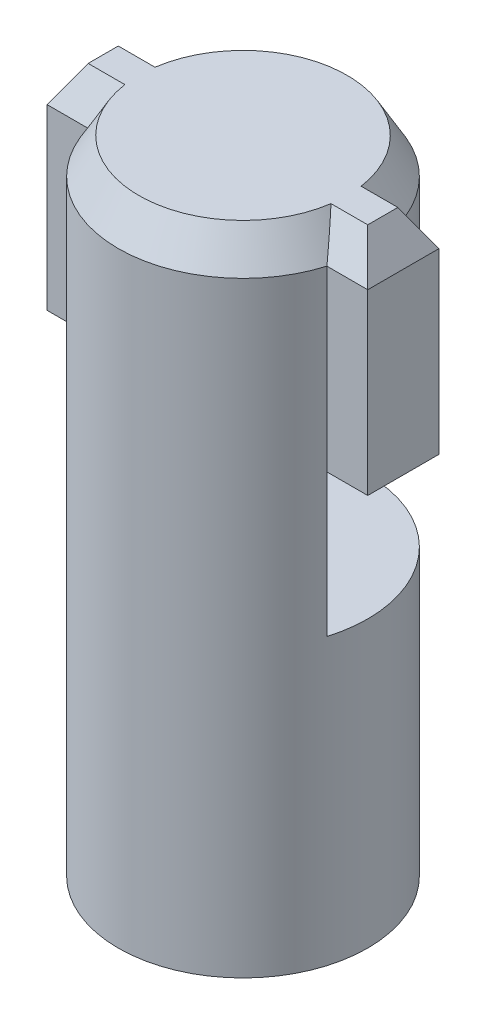
SolidWorks part; units mm, degrees
ref_plane "Спереди" through (0, 0, 0) normal (0, 0, 1) x (1, 0, 0)
ref_plane "Сверху" through (0, 0, 0) normal (0, 1, 0) x (1, 0, 0)
ref_plane "Справа" through (0, 0, 0) normal (1, 0, 0) x (0, 0, -1)
sketch "Sketch1" plane through (0, 0, 0) normal (0, 1, 0) x (1, 0, 0)
  circle A0 centre (0, 0) radius 3.5
  dimension "D1" = 7
extrude "Boss-Extrude1" add sketch "Sketch1" along normal blind 18
sketch "Sketch2" plane through (0, 18, 0) normal (0, 1, 0) x (1, 0, 0)
  line L1 (4.5, 1) -> (-4.5, 1)
  line L2 (4.5, 1) -> (4.5, -1)
  line L3 (4.5, -1) -> (-4.5, -1)
  line L4 (-4.5, 1) -> (-4.5, -1)
  line L5 (4.5, 1) -> (-4.5, -1) construction
  line L6 (4.5, -1) -> (-4.5, 1) construction
  point P0 (0, 0)
  dimension "D1" = 2
  dimension "D2" = 9
extrude "Boss-Extrude3" add sketch "Sketch2" against normal blind 10
sketch "Sketch3" plane through (0, 0, 0) normal (0, -1, 0) x (1, 0, 0)
  line L0 (3.3541, 1) -> (-3.3541, 1) construction
  line L1 (-3.5, 0) -> (3.5, 0) construction
  line L3 (-5, 1) -> (5, 1)
  line L4 (-5, 1) -> (-5, -3.5)
  line L5 (-5, -3.5) -> (5, -3.5)
  line L6 (5, 1) -> (5, -3.5)
  line L7 (-5, 1) -> (5, -3.5) construction
  line L8 (-5, -3.5) -> (5, 1) construction
  circle A0 centre (0, 0) radius 3.5 construction
  point P7 (0, -1.25)
  point P12 (0, 1)
  point P13 (0, 1)
  point P16 (0, -3.5)
  dimension "D1" = 2
  dimension "D2" = 10
extrude "Cut-Extrude3" cut sketch "Sketch3" against normal blind 4 from offset 8 offset against normal yes
chamfer "Chamfer1" distance 1 angle 30 8 edges at (-3.9271, 18, 1) (-4.5, 18, 0) (-3.9271, 18, -1) (0, 18, -3.5) (3.9271, 18, -1) (4.5, 18, 0) (3.9271, 18, 1) (0, 18, 3.5) first distance on face at (-3.9271, 15, 1) first distance on face at (-4.5, 15, 0) first distance on face at (-3.9271, 15, -1) first distance on face at (0, 15, -2.25) first distance on face at (3.9271, 15, -1) first distance on face at (4.5, 15, 0) first distance on face at (3.9271, 15, 1) first distance on face at (0, 12.6667, 0.6667)
